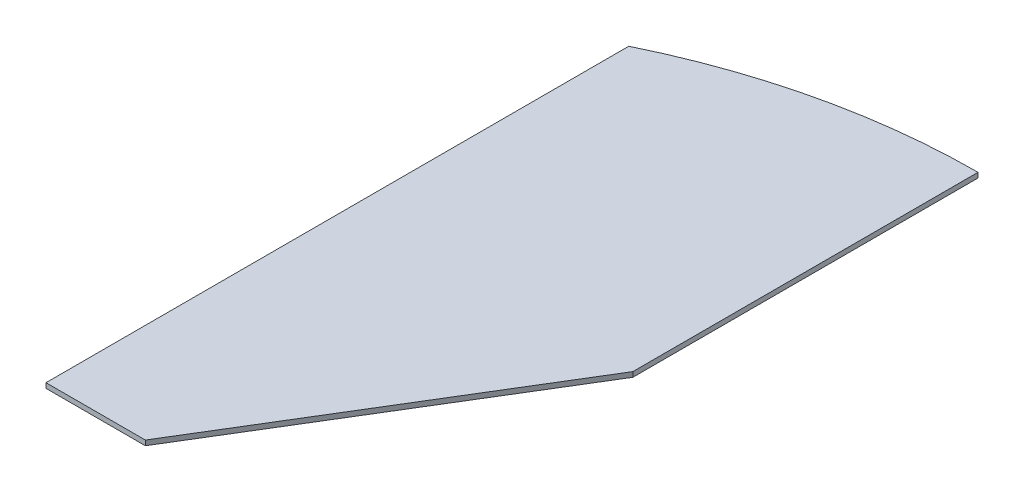
SolidWorks part; units mm, degrees
ref_plane "Front Plane" through (0, 0, 0) normal (0, 0, 1) x (1, 0, 0)
ref_plane "Top Plane" through (0, 0, 0) normal (0, 1, 0) x (1, 0, 0)
ref_plane "Right Plane" through (0, 0, 0) normal (1, 0, 0) x (0, 0, -1)
sketch "Sketch1" plane through (0, 0, 0) normal (0, 1, 0) x (1, 0, 0)
  line L0 (-0.8458, -19.2201) -> (12.1542, 2.134)
  line L3 (-0.8458, -19.2201) -> (-7.8458, -19.2201)
  line L4 (-7.8458, 21.8456) -> (-7.8458, -19.2201)
  line L5 (12.1542, 2.134) -> (12.1542, 26.4569)
  arc A0 (12.1542, 26.4569) -> (-7.8458, 21.8456) centre (12.1542, -19.2201) ccw
  point P0 (0, 0)
  point P4 (5.6542, -8.5431)
  dimension "D4" = 7
  dimension "D2" = 20
  dimension "D1" = 24.3229
  dimension "D3" = 25
  dimension "D5" = 35
  dimension "D6" = 41.0657
extrude "Boss-Extrude1" add sketch "Sketch1" along normal blind 0.35
scale "Scale1" scale about centroid uniform scaling yes scale factor 10
